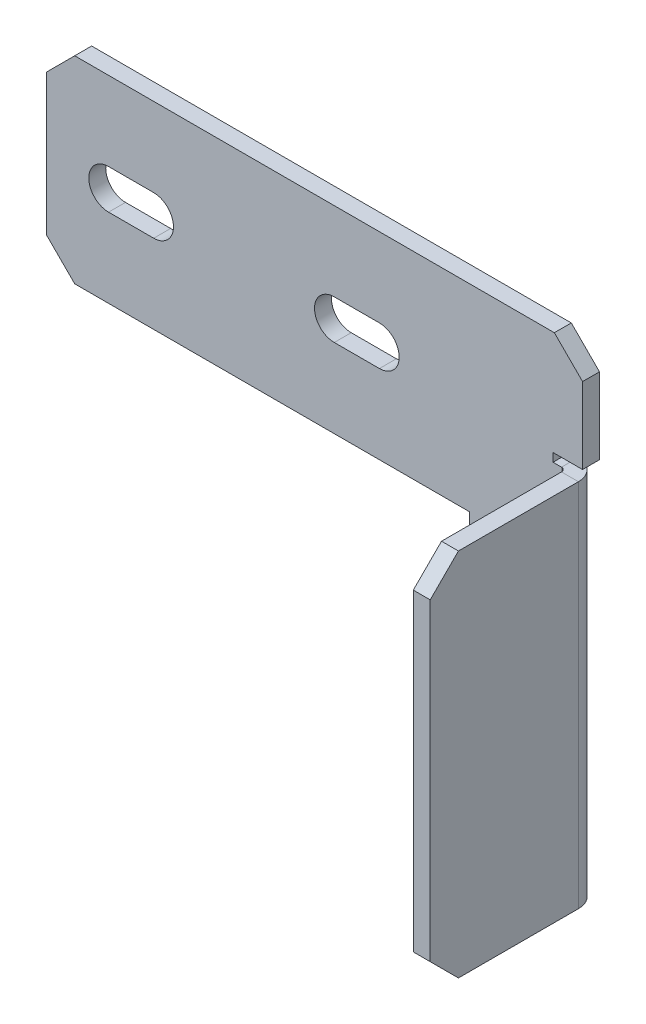
SolidWorks part; units mm, degrees
note: The reader was unsure of these and kept them because the rebuilt part matched: flange length of "边线-法兰1".
material "Q235-A"
ref_plane "前视基准面" through (0, 0, 0) normal (0, 0, 1) x (1, 0, 0)
ref_plane "上视基准面" through (0, 0, 0) normal (0, 1, 0) x (1, 0, 0)
ref_plane "右视基准面" through (0, 0, 0) normal (1, 0, 0) x (0, 0, -1)
sketch "草图1" plane through (0, 0, 0) normal (0, 0, 1) x (1, 0, 0)
  line L0 (75, -35) -> (75, -85.5331)
  line L1 (0, 0) -> (95, 0)
  line L2 (0, 0) -> (0, -35)
  line L3 (0, -35) -> (75, -35)
  line L5 (75, -85.5331) -> (95, -85.5331)
  line L6 (95, -85.5331) -> (95, 0)
  dimension "D1" = 35
  dimension "D2" = 95
  dimension "D3" = 20
base flange "基体-法兰1" sketch "草图1" thickness 3 reverse thickness direction no parameters "D1"=0.7366
edge flange "边线-法兰1" sketch "草图8" flange angle 90 flange length 30 flange position material inside bend radius 0.7366 thickness 3 relief rectangular parameters "D6"=10
sketch "草图8" plane through (95, 0, 0) normal (1, 0, 0) x (0, 1, 0)
  line L0 (-85.5331, 0) -> (0, 0) construction
  line L1 (-85.5331, 0) -> (-20, 0)
  line L2 (-85.5331, 0) -> (-85.5331, 27)
  line L3 (-85.5331, 27) -> (-20, 27)
  line L4 (-20, 27) -> (-20, 0)
  point P4 (-11.1468, 0)
  dimension "D1" = 20
bend "边线折弯1" bend radius 0.7366 bend angle 90 parameters "D5"=1
chamfer "倒角1" distance 5 angle 45 6 edges at (75, -85.5331, -1.5) (0, -35, -1.5) (0, 0, -1.5) (95, 0, -1.5) (93.5, -85.5331, 27) (93.5, -20, 27)
sketch "草图10" plane through (0, 0, 0) normal (0, 0, 1) x (1, 0, 0)
  line L0 (0, -17.5) -> (100.8278, -17.5) construction
  line L1 (0, -5) -> (0, -30) construction
  line L2 (11, -17.5) -> (19, -17.5) construction
  line L3 (11, -14) -> (19, -14)
  line L4 (11, -21) -> (19, -21)
  line L5 (51, -17.5) -> (59, -17.5) construction
  line L6 (51, -14) -> (59, -14)
  line L7 (51, -21) -> (59, -21)
  arc A0 (11, -14) -> (11, -21) centre (11, -17.5) ccw
  arc A1 (19, -21) -> (19, -14) centre (19, -17.5) ccw
  arc A2 (51, -14) -> (51, -21) centre (51, -17.5) ccw
  arc A3 (59, -21) -> (59, -14) centre (59, -17.5) ccw
  point P6 (15, -17.5)
  point P13 (55, -17.5)
  point P18 (0, 0)
  point P19 (17.7067, -17.5)
  point P20 (12.0807, -11.9895)
  dimension "D1" = 7
  dimension "D2" = 7
  dimension "D3" = 8
  dimension "D4" = 8
  dimension "D5" = 15
  dimension "D6" = 40
extrude "切除-拉伸1" cut sketch "草图10" against normal blind 10 normal cut yes
sketch "折弯-线1" [suppressed] plane through (0, 0, 0) normal (0, 1, 0) x (1, 0, 0)
sketch "边界框1" [suppressed] plane through (0, 0, 0) normal (0, 1, 0) x (1, 0, 0)
sheet metal parameters "钣金1" thickness 3 parameters "D1"=0.7366
flat pattern "平板型式1" [suppressed]
sketch "折弯-线2" plane through (0, 0, 0) normal (0, 1, 0) x (1, 0, 0)
sketch3d "边界框2" [suppressed]
  line L0 (0, -85.5331, 0) -> (-100, -85.5331, 0) construction
  line L1 (0, 0, 0) -> (-100, 0, 0) construction
  line L2 (0, -85.5331, 0) -> (0, 0, 0) construction
  line L3 (-100, -85.5331, 0) -> (-100, 0, 0) construction
sheet metal parameters "钣金2" thickness 3 parameters "D1"=0.7366
flat pattern "平板型式1"
sketch "折弯-线2" plane through (0, 0, 0) normal (0, 0, 1) x (1, 0, 0)
  line L0 (98.02, -85.5331) -> (98.02, -20) construction
  line L1 (98.02, -85.5331) -> (98.02, -20) construction
sketch3d "边界框2" [suppressed]
  line L0 (0, -85.5331, 0) -> (126.04, -85.5331, 0) construction
  line L1 (0, 0, 0) -> (126.04, 0, 0) construction
  line L2 (0, -85.5331, 0) -> (0, 0, 0) construction
  line L3 (126.04, -85.5331, 0) -> (126.04, 0, 0) construction
bend of the flat pattern "展平-<边线折弯1>1"
sheet metal parameters "钣金3" thickness 3 parameters "D1"=0.7366
flat pattern "平板型式1"
sketch "折弯-线2" plane through (0, 0, 0) normal (0, 0, 1) x (1, 0, 0)
  line L0 (93.02, -85.5331) -> (93.02, -20) construction
  line L1 (93.02, -85.5331) -> (93.02, -20) construction
sketch3d "边界框2" [suppressed]
  line L0 (0, -85.5331, 0) -> (121.04, -85.5331, 0) construction
  line L1 (0, 0, 0) -> (121.04, 0, 0) construction
  line L2 (0, -85.5331, 0) -> (0, 0, 0) construction
  line L3 (121.04, -85.5331, 0) -> (121.04, 0, 0) construction
bend of the flat pattern "展平-<边线折弯1>1"
